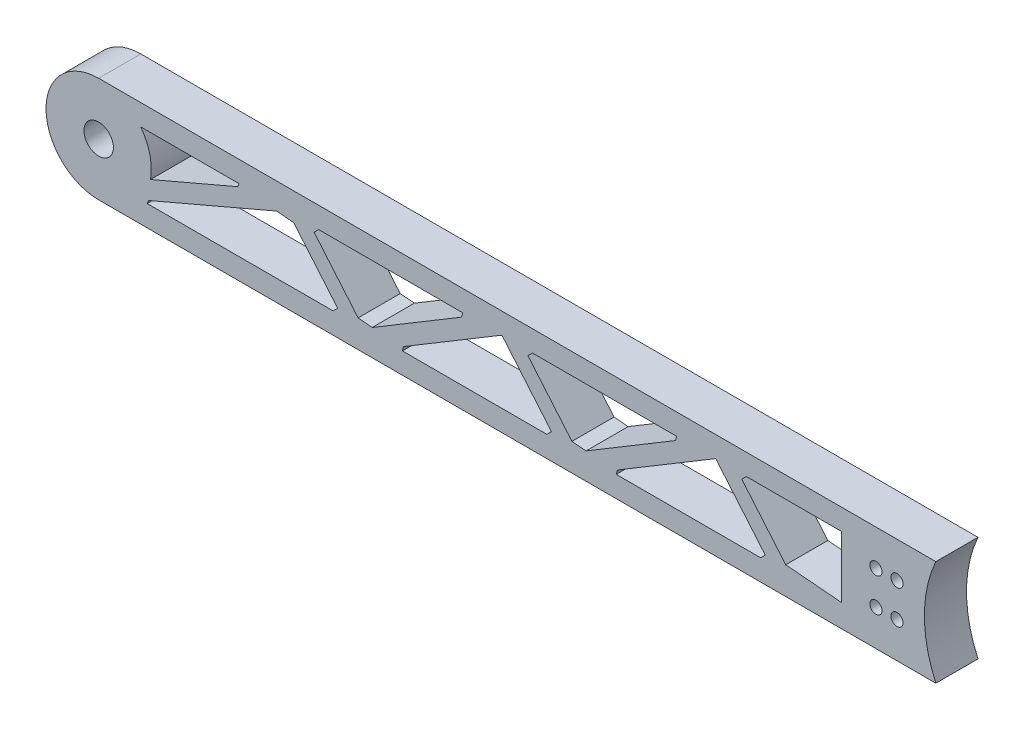
SolidWorks part; units mm, degrees
material "ABS"
ref_plane "前视基准面" through (0, 0, 0) normal (0, 0, 1) x (1, 0, 0)
ref_plane "上视基准面" through (0, 0, 0) normal (0, 1, 0) x (1, 0, 0)
ref_plane "右视基准面" through (0, 0, 0) normal (1, 0, 0) x (0, 0, -1)
other "Configuration Table"
sketch "草图1" plane through (0, 0, 0) normal (0, 0, 1) x (1, 0, 0)
  line L0 (0, 0) -> (223, 0) construction
  line L1 (0, 12.5) -> (199.0678, 12.5)
  line L2 (0, -12.5) -> (199.0678, -12.5)
  arc A0 (0, 12.5) -> (0, -12.5) centre (0, 0) ccw
  arc A1 (199.0678, -12.5) -> (199.0678, 12.5) centre (223, 0) ccw
  dimension "D1" = 12.5
  dimension "D2" = 27
  dimension "D3" = 223
extrude "凸台-拉伸1" add sketch "草图1" along normal blind 10
sketch "草图3" plane through (0, 0, 10) normal (0, 0, 1) x (1, 0, 0)
  line L0 (176.3768, 7.5) -> (176.3768, -7.5)
  line L1 (10, 7.5) -> (196.3768, 7.5)
  line L2 (10, -7.5) -> (198.0625, -7.5)
  line L3 (199.0678, 12.5) -> (0, 12.5) construction
  line L4 (0, -12.5) -> (199.0678, -12.5) construction
  line L5 (10, -7.5) -> (45, 7.5)
  line L6 (34.8456, 7.5) -> (12.3125, -2.1571)
  line L7 (45, 7.5) -> (57.6414, -7.5)
  line L8 (50.231, 7.5) -> (62.8724, -7.5)
  line L9 (62.8724, -7.5) -> (87.8724, 7.5)
  line L10 (70.647, -7.5) -> (95.647, 7.5)
  line L11 (113.6246, -7.5) -> (138.6246, 7.5)
  line L12 (95.7522, 7.5) -> (108.3936, -7.5)
  line L13 (100.9832, 7.5) -> (113.6246, -7.5)
  line L14 (121.3992, -7.5) -> (146.3992, 7.5)
  line L16 (146.5044, 7.5) -> (159.1458, -7.5)
  line L17 (151.7355, 7.5) -> (164.3768, -7.5)
  line L19 (164.3768, -7.5) -> (189.3768, 7.5)
  line L20 (172.1514, -7.5) -> (197.1514, 7.5)
  circle A0 centre (0, 0) radius 12.5
  circle A1 centre (222.9812, 2.895) radius 27
  point P5 (10, 7.5)
  dimension "D2" = 25
  dimension "D3" = 54
  dimension "D1" = 223
  dimension "D4" = 5
  dimension "D5" = 5
  dimension "D6" = 4
  dimension "D7" = 4
  dimension "D8" = 4
  dimension "D9" = 3
  dimension "D10" = 12
  dimension "D11" = 20
  dimension "D12" = 106.924
  dimension "D13" = 35
  dimension "D14" = 25
extrude "切除-拉伸1" cut sketch "草图3" against normal through all and the other way through all
sketch "草图7" plane through (0, 0, 0) normal (0, 0, -1) x (-1, 0, 0)
  circle A0 centre (0, 0) radius 3.5
  dimension "D1" = 7
extrude "切除-拉伸5" cut sketch "草图7" against normal through all
sketch "草图8" plane through (0, 0, 0) normal (0, 0, -1) x (-1, 0, 0)
  line L0 (0, 0) -> (-223, 0) construction
  circle A0 centre (-223, 0) radius 5
  dimension "D1" = 10
extrude "切除-拉伸6" cut sketch "草图8" against normal blind 3
sketch "草图9" plane through (0, 0, 0) normal (0, 0, -1) x (-1, 0, 0)
  line L0 (0, 0) -> (-223, 0)
  circle A0 centre (-223, 0) radius 3
  dimension "D1" = 6
  dimension "D2" = 223
extrude "切除-拉伸7" cut sketch "草图9" against normal through all
sketch "草图11" plane through (0, 0, 10) normal (0, 0, 1) x (1, 0, 0)
  circle A0 centre (223, 0) radius 27
extrude "切除-拉伸9" cut sketch "草图11" against normal blind 10
sketch "草图12" plane through (0, 0, 10) normal (0, 0, 1) x (1, 0, 0)
  line L0 (0, 0) -> (226, 0) construction
  circle A1 centre (226, 0) radius 30
  dimension "D1" = 226
extrude "切除-拉伸10" cut sketch "草图12" against normal blind 10
sketch "草图13" plane through (0, 0, 10) normal (0, 0, 1) x (1, 0, 0)
  line L0 (0, 0) -> (226, 0) construction
  circle A0 centre (226, 0) radius 30
  point P4 (196, 0)
  point P5 (175.9339, 0)
  dimension "D1" = 226
sketch "草图14" plane through (0, 0, 10) normal (0, 0, 1) x (1, 0, 0)
  line L0 (196, -12.5) -> (196, 12.5) construction
  line L1 (0, -12.5) -> (198.7282, -12.5) construction
  line L2 (198.7282, 12.5) -> (0, 12.5) construction
  line L3 (196, 12.5) -> (181, 12.5)
  line L4 (196, 12.5) -> (193, 12.5)
  line L5 (193, 12.5) -> (193, -12.5)
  line L6 (181, 12.5) -> (181, -12.5)
  line L7 (181, -4) -> (193, -4) construction
  line L8 (184.5, 12.5) -> (184.5, -12.5) construction
  line L9 (189.5, 12.5) -> (189.5, -12.5) construction
  line L10 (181, 4) -> (193, 4) construction
  circle A0 centre (226, 0) radius 30 construction
  circle A7 centre (189.5, -4) radius 1.45
  circle A8 centre (184.5, -4) radius 1.45
  circle A9 centre (184.5, 4) radius 1.45
  circle A10 centre (189.5, 4) radius 1.45
  dimension "D6" = 8.5
  dimension "D7" = 2.9
  dimension "D1" = 15
  dimension "D2" = 3.5
  dimension "D3" = 3
  dimension "D4" = 3.5
  dimension "D5" = 8.5
extrude "切除-拉伸12" cut sketch "草图14" against normal blind 300 contours A9 | A10 | A7 | A8
chamfer "倒角1" distance 2 angle 45 16 edges at (164.3768, -7.5, 5) (151.7355, 7.5, 5) (159.1458, -7.5, 5) (121.3992, -7.5, 5) (113.6246, -7.5, 5) (138.6246, 7.5, 5) (100.9832, 7.5, 5) (70.647, -7.5, 5) (108.3936, -7.5, 5) (87.8724, 7.5, 5) (62.8724, -7.5, 5) (50.231, 7.5, 5) (57.6414, -7.5, 5) (45, 7.5, 5) (34.8456, 7.5, 5)
sketch "草图15" plane through (0, 0, 0) normal (0, 0, -1) x (-1, 0, 0)
  circle A0 centre (0, 0) radius 5.25
  circle M6 centre (0, 0) radius 3.5
  dimension "D1" = 10.5
extrude "切除-拉伸13" cut sketch "草图15" against normal blind 3 contours A0 M6
